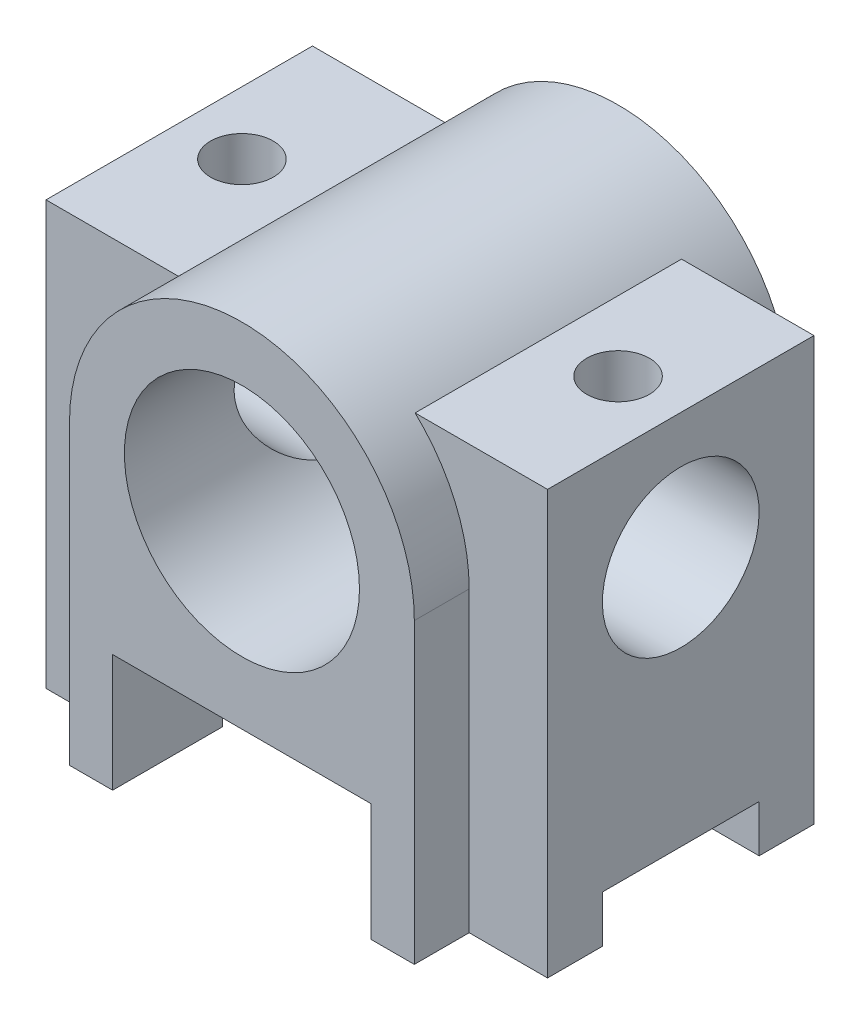
SolidWorks part; units mm, degrees
ref_plane "Front Plane" through (0, 0, 0) normal (0, 0, 1) x (1, 0, 0)
ref_plane "Top Plane" through (0, 0, 0) normal (0, 1, 0) x (1, 0, 0)
ref_plane "Right Plane" through (0, 0, 0) normal (1, 0, 0) x (0, 0, -1)
sketch "Sketch1" plane through (0, 0, 0) normal (0, 0, 1) x (1, 0, 0)
  line L0 (-22, 0) -> (-22, -38)
  line L1 (-22, -38) -> (-16.5, -38)
  line L2 (-16.5, -38) -> (-16.5, -23)
  line L3 (-16.5, -23) -> (16.5, -23)
  line L4 (16.5, -23) -> (16.5, -38)
  line L5 (16.5, -38) -> (22, -38)
  line L6 (22, -38) -> (22, 0)
  arc A0 (22, 0) -> (-22, 0) centre (0, 0) ccw
  circle A1 centre (0, 0) radius 15
  dimension "D4" = 30
  dimension "D1" = 44
  dimension "D2" = 33
  dimension "D3" = 15
  dimension "D5" = 38
extrude "Boss-Extrude1" add sketch "Sketch1" against normal blind 48
sketch "Sketch2" plane through (22, 0, 0) normal (1, 0, 0) x (0, 0, -1)
  line L0 (48, -38) -> (0, -38) construction
  line L1 (7, -38) -> (41, -38)
  line L2 (7, -38) -> (7, 16)
  line L3 (7, 16) -> (41, 16)
  line L4 (41, -38) -> (41, 16)
  line L5 (24, 22) -> (24, -38) construction
  line L6 (48, 22) -> (0, 22) construction
  line L7 (48, 0) -> (0, 0) construction
  line L8 (48, -38) -> (48, 0) construction
  line L10 (14, -38) -> (34, -38)
  line L11 (14, -38) -> (14, -32)
  line L12 (14, -32) -> (34, -32)
  line L13 (34, -38) -> (34, -32)
  circle A0 centre (24, 0) radius 10
  point P20 (24, -32)
  line M2 (0, -38) -> (48, -38)
  line M4 (48, 0) -> (0, 0)
  dimension "D1" = 20
  dimension "D2" = 7
  dimension "D3" = 6
  dimension "D4" = 34
  dimension "D5" = 20
  dimension "D6" = 54
ref_plane "Plane2" through (0, 0, 0) normal (-1, 0, 0) x (0, 0, 1)
extrude "Boss-Extrude3" add sketch "Sketch2" against normal blind 6.9 contours L5 L3 L2 A0 M4 | L3 L5 A0 L4 M4 region at (22, 9.5248, -13.7722) region at (22, 9.5248, -34.2278)
extrude "Boss-Extrude4" add sketch "Sketch2<4>" along normal blind 10 contours L3 L5 A0 L4 M4 | L5 L3 L2 A0 M4 | L5 A0 L2 L11 L12 M4 M2 | A0 L5 L12 L13 L4 M2 M4 region at (22, -19.392, -14.4275) region at (22, 9.5248, -13.7722) region at (22, -19.392, -33.5725) region at (22, 9.5248, -34.2278)
sketch "Sketch2<4>" plane through (22, 0, 0) normal (1, 0, 0) x (0, 0, -1) same geometry as "Sketch2"
mirror "Mirror2" about plane through (0, 0, 0) normal (-1, 0, 0) of "Boss-Extrude1", "Boss-Extrude4", "Boss-Extrude3"
extrude "Cut-Extrude1" cut sketch "Sketch2<5>" against normal through all contours L5 A0 M4 | A0 L5 M4 | L5 A0 M4 | L5 A0 M4 | L11 L10 L13 L12 region at (22, -4.2441, -19.7559) region at (22, 4.2441, -19.7559) region at (22, 4.2441, -28.2441) region at (22, -4.2441, -28.2441)
sketch "Sketch2<5>" plane through (22, 0, 0) normal (1, 0, 0) x (0, 0, -1) same geometry as "Sketch2"
sketch "Sketch3" plane through (0, 16, 0) normal (0, 1, 0) x (1, 0, 0)
  line L0 (32, 24) -> (-32, 24) construction
  line L1 (32, 7) -> (32, 41) construction
  line L2 (-32, 7) -> (-32, 41) construction
  circle A0 centre (24, 24) radius 4
  circle A1 centre (-24, 24) radius 4
  point P6 (0, 0)
  point P7 (0, 0)
  point P22 (0, 0)
  point P25 (0, 0)
  point P30 (0, 0)
  point P31 (0, 0)
  point P32 (0, 0)
  point P35 (0, 0)
  point P36 (0, 0)
  point P37 (0, 0)
  point P38 (0, 0)
  point P39 (0, 0)
  dimension "D1" = 8
  dimension "D3" = 8
  dimension "D2" = 48
extrude "Cut-Extrude2" cut sketch "Sketch3" against normal blind 10
